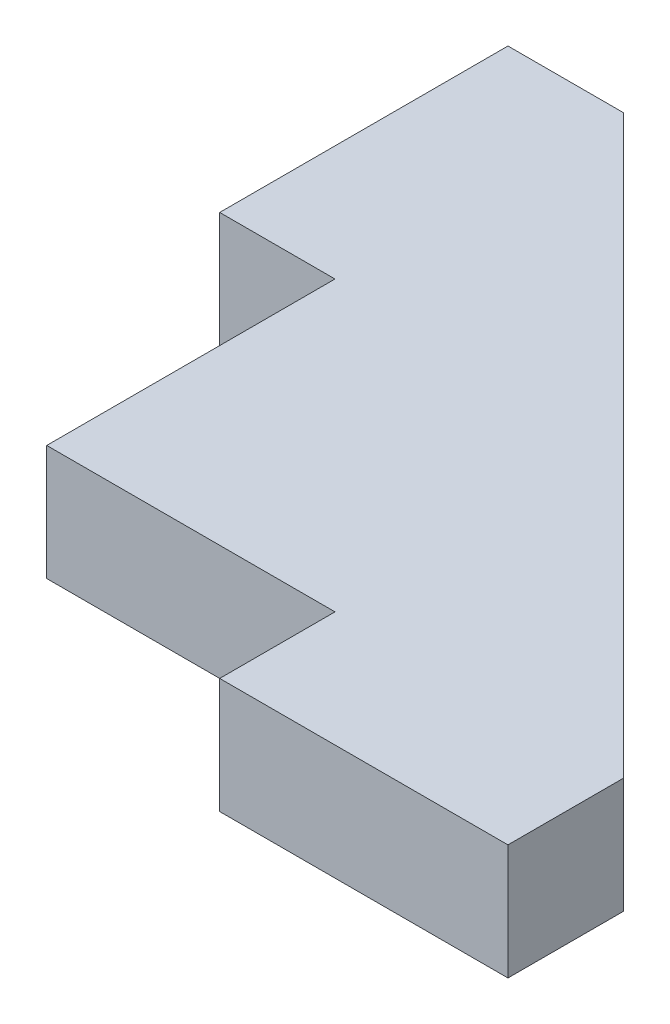
SolidWorks part; units mm, degrees
ref_plane "Front Plane" through (0, 0, 0) normal (0, 0, 1) x (1, 0, 0)
ref_plane "Top Plane" through (0, 0, 0) normal (0, 1, 0) x (1, 0, 0)
ref_plane "Right Plane" through (0, 0, 0) normal (1, 0, 0) x (0, 0, -1)
sketch "Sketch1" plane through (0, 0, 0) normal (0, 1, 0) x (1, 0, 0)
  line L0 (0, 0) -> (10, 0)
  line L1 (10, 0) -> (0, 10)
  line L2 (0, 10) -> (0, 0)
  line L4 (0, 10) -> (-2, 10)
  line L5 (0, 10) -> (0, 5)
  line L6 (0, 5) -> (-2, 5)
  line L7 (-2, 10) -> (-2, 5)
  line L8 (10, 0) -> (5, 0)
  line L9 (10, 0) -> (10, -2)
  line L10 (10, -2) -> (5, -2)
  line L11 (5, 0) -> (5, -2)
  dimension "D1" = 10
  dimension "D2" = 10
  dimension "D3" = 5
  dimension "D4" = 5
  dimension "D5" = 2
  dimension "D6" = 2
extrude "Boss-Extrude1" add sketch "Sketch1" along normal blind 2 contours L1 L2 L0 | L4 L7 L6 L2 | L0 L11 L10 L9 region at (3.3333, 0, -3.3333) region at (7.5, 0, 1) region at (-1, 0, -7.5)
